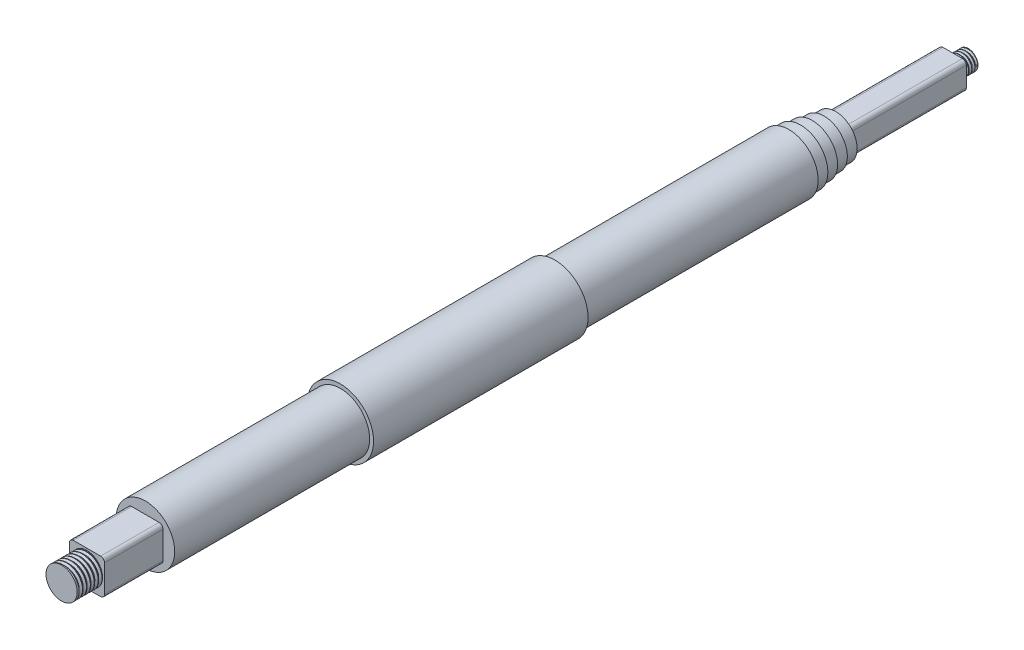
SolidWorks part; units mm, degrees
ref_plane "Front Plane" through (0, 0, 0) normal (0, 0, 1) x (1, 0, 0)
ref_plane "Top Plane" through (0, 0, 0) normal (0, 1, 0) x (1, 0, 0)
ref_plane "Right Plane" through (0, 0, 0) normal (1, 0, 0) x (0, 0, -1)
sketch "Sketch1" plane through (0, 0, 0) normal (0, 1, 0) x (1, 0, 0)
  line L0 (0, 0) -> (0, 177) construction
  line L3 (7.5, 0) -> (0, 0)
  line L4 (7.5, 0) -> (7.5, 50)
  line L5 (7.5, 50) -> (8.5, 50)
  line L6 (8.5, 50) -> (8.5, 105)
  line L7 (8.5, 105) -> (7.5, 105)
  line L8 (7.5, 105) -> (7.5, 165)
  line L9 (7.5, 165) -> (7, 165)
  line L10 (7, 165) -> (7, 168)
  line L11 (7, 168) -> (6.5, 168)
  line L12 (6.5, 168) -> (6.5, 171)
  line L13 (6.5, 171) -> (6, 171)
  line L14 (6, 171) -> (6, 174)
  line L15 (6, 174) -> (5.5, 174)
  line L16 (5.5, 174) -> (5.5, 177)
  line L17 (0, 177) -> (5.5, 177)
  line L18 (0, 0) -> (0, 177)
  point P1 (0, 62.3561)
  dimension "D1" = 7.5
  dimension "D2" = 8.5
  dimension "D3" = 7.5
  dimension "D4" = 0.5
  dimension "D5" = 0.5
  dimension "D6" = 0.5
  dimension "D7" = 0.5
  dimension "D8" = 3
  dimension "D9" = 3
  dimension "D10" = 3
  dimension "D11" = 3
  dimension "D12" = 50
  dimension "D13" = 60
  dimension "D14" = 55
revolve "Revolve1" add sketch "Sketch1" angle 360 about L0
sketch "Sketch3" plane through (0, 0, 0) normal (0, 0, 1) x (1, 0, 0)
  line L1 (-4.5, -4.5) -> (4.5, -4.5)
  line L2 (-4.5, -4.5) -> (-4.5, 4.5)
  line L3 (-4.5, 4.5) -> (4.5, 4.5)
  line L4 (4.5, -4.5) -> (4.5, 4.5)
  line L5 (0, 4.5) -> (0, -4.5) construction
  line L6 (-4.5, 0) -> (4.5, 0) construction
  point P0 (0, 0)
  dimension "D1" = 9
extrude "Boss-Extrude1" add sketch "Sketch3" along normal blind 15
sketch "Sketch4" plane through (0, 0, 15) normal (0, 0, 1) x (1, 0, 0)
  circle A0 centre (0, 0) radius 4
  dimension "D1" = 8
extrude "Boss-Extrude2" add sketch "Sketch4" along normal blind 6.5
sketch "Sketch5" plane through (0, 0, -177) normal (0, 0, -1) x (-1, 0, 0)
  line L1 (-3.5, -3.5) -> (3.5, -3.5)
  line L2 (-3.5, -3.5) -> (-3.5, 3.5)
  line L3 (-3.5, 3.5) -> (3.5, 3.5)
  line L4 (3.5, -3.5) -> (3.5, 3.5)
  line L5 (0, 3.5) -> (0, -3.5) construction
  line L6 (-3.5, 0) -> (3.5, 0) construction
  point P0 (0, 0)
  dimension "D1" = 7
extrude "Boss-Extrude3" add sketch "Sketch5" along normal blind 30
sketch "Sketch6" plane through (0, 0, -207) normal (0, 0, -1) x (-1, 0, 0)
  circle A0 centre (0, 0) radius 2.5
  dimension "D1" = 5
extrude "Boss-Extrude4" add sketch "Sketch6" along normal blind 4
fillet "Fillet2" radius 1 4 edges at (-4.5, -4.5, 7.5) (-4.5, 4.5, 7.5) (4.5, 4.5, 7.5) (4.5, -4.5, 7.5)
fillet "Fillet3" radius 1 4 edges at (3.5, 3.5, -192) (-3.5, 3.5, -192) (3.5, -3.5, -192) (-3.5, -3.5, -192)
thread "Thread1" pitch 1 method cut profile "Thread Profile1" start angle 0, offset 0, length 0, pitch 1, diameter 8
ref_plane "Plane1" through (-4, 0, 21.5) normal (0, -1, 0) x (-1, 0, 0)
sketch "Thread Profile1" plane through (-4, 0, 21.5) normal (0, -1, 0) x (-1, 0, 0)
  line L0 (0, 0) -> (0, 1) construction
  line L11 (0, 0) -> (0, 0.875)
  line L12 (0, 0.875) -> (-0.5413, 0.5625)
  line L13 (-0.5413, 0.5625) -> (-0.5413, 0.3125)
  line L15 (-0.5413, 0.3125) -> (0, 0)
  line L17 (-0.5413, 0.4375) -> (0, 0.4375) construction
  point P2 (0, 0)
  dimension "Pitch" = 1
  dimension "Profile_Angle" = 60
  dimension "Profile_Land" = 0.25
  dimension "Profile_Height" = 0.5413
thread "Thread2" pitch 0.8 method cut profile "Thread Profile2" start angle 0, offset 0, length 0, pitch 0.8, diameter 5
ref_plane "Plane2" through (2.5, 0, -211) normal (0, -1, 0) x (1, 0, 0)
sketch "Thread Profile2" plane through (2.5, 0, -211) normal (0, -1, 0) x (1, 0, 0)
  line L0 (0, 0) -> (0, 0.8) construction
  line L11 (0, 0) -> (0, 0.7)
  line L12 (0, 0.7) -> (-0.433, 0.45)
  line L13 (-0.433, 0.45) -> (-0.433, 0.25)
  line L15 (-0.433, 0.25) -> (0, 0)
  line L17 (-0.433, 0.35) -> (0, 0.35) construction
  point P2 (0, 0)
  dimension "Pitch" = 0.8
  dimension "Profile_Angle" = 60
  dimension "Profile_Land" = 0.2
  dimension "Profile_Height" = 0.433
